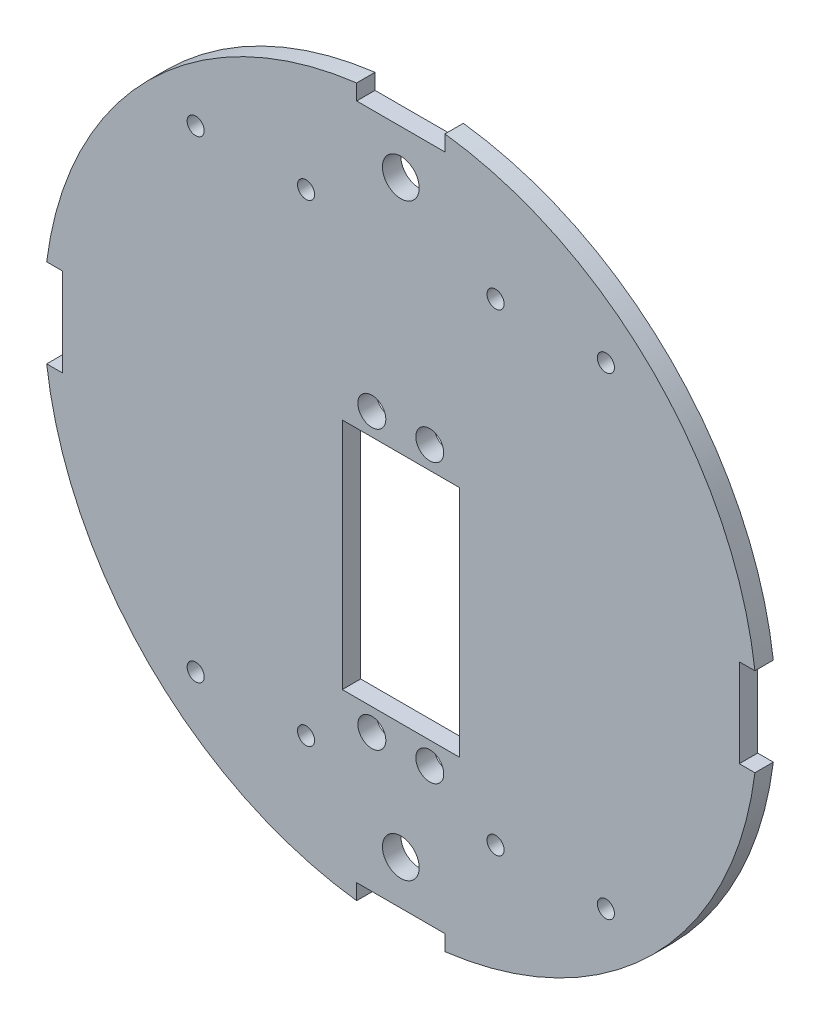
SolidWorks part; units mm, degrees
material "A-Glass Fiber"
ref_plane "Front Plane" through (0, 0, 0) normal (0, 0, 1) x (1, 0, 0)
ref_plane "Top Plane" through (0, 0, 0) normal (0, 1, 0) x (1, 0, 0)
ref_plane "Right Plane" through (0, 0, 0) normal (1, 0, 0) x (0, 0, -1)
sketch "Sketch1" plane through (0, 0, 0) normal (0, 0, 1) x (1, 0, 0)
  circle A0 centre (0, 0) radius 61.595
extrude "Boss-Extrude1" add sketch "Sketch1" along normal blind 3.175
sketch "Sketch2" plane through (0, 0, 3.175) normal (0, 0, 1) x (1, 0, 0)
  line L0 (0, 0) -> (0, 61.595) construction
  line L2 (-7.62, 58.42) -> (7.62, 58.42)
  line L3 (-7.62, 58.42) -> (-7.62, 64.77)
  line L4 (-7.62, 64.77) -> (7.62, 64.77)
  line L5 (7.62, 58.42) -> (7.62, 64.77)
  line L6 (-7.62, 58.42) -> (7.62, 64.77) construction
  line L7 (-7.62, 64.77) -> (7.62, 58.42) construction
  circle A0 centre (0, 0) radius 61.595 construction
  circle A1 centre (0, 50.8) radius 3.175
  dimension "D3" = 50.8
  dimension "D1" = 15.24
  dimension "D2" = 6.35
extrude "Cut-Extrude1" cut sketch "Sketch2" against normal blind 3.175 contours L5 L4 L3 L2 | A1
pattern_circular "CirPattern1" count 4 every 90 about axis through (0, 0, 3.175) along (0, 0, 1) of "Cut-Extrude1"
sketch "Sketch3" plane through (0, 0, 3.175) normal (0, 0, 1) x (1, 0, 0)
  line L2 (-10.1, 9.5) -> (-10.1, -29.8)
  line L3 (10.1, 9.5) -> (-10.1, 9.5)
  line L6 (10.1, -29.8) -> (10.1, 8.5)
  line L7 (-9.1, -30.8) -> (9.1, -30.8)
  line L8 (-9.1, -30.8) -> (-10.1, -30.8)
  line L9 (-10.1, -30.8) -> (-10.1, -29.8)
  line L10 (9.1, -30.8) -> (10.1, -30.8)
  line L11 (10.1, -30.8) -> (10.1, -29.8)
  line L12 (10.1, 8.5) -> (10.1, 9.5)
extrude "Cut-Extrude2" cut sketch "Sketch3" against normal blind 3.175
sketch "Sketch4" plane through (0, 0, 0) normal (0, 0, -1) x (-1, 0, 0)
  circle A0 centre (5, -34.65) radius 2.413
  circle A1 centre (-5, -34.65) radius 2.413
  circle A2 centre (-5, 13.35) radius 2.413
  circle A3 centre (5, 13.35) radius 2.413
extrude "Cut-Extrude3" cut sketch "Sketch4" against normal blind 3.175
sketch "Sketch5" plane through (0, 0, 0) normal (0, 0, -1) x (-1, 0, 0)
  circle A0 centre (-50.8, 0) radius 3.175
  circle A1 centre (50.8, 0) radius 3.175
extrude "Boss-Extrude2" add sketch "Sketch5" against normal blind 3.175
sketch "Sketch6" plane through (0, 0, 3.175) normal (0, 0, 1) x (1, 0, 0)
  line L0 (0, 58.42) -> (0, -58.42) construction
  line L1 (-7.62, 58.42) -> (7.62, 58.42) construction
  line L2 (7.62, -58.42) -> (-7.62, -58.42) construction
  circle A0 centre (16.3543, 40.8119) radius 1.4732 construction
  circle A1 centre (35.4043, 40.8119) radius 1.4732 construction
  circle A2 centre (35.4043, -40.8119) radius 1.4732 construction
  circle A3 centre (16.3543, -40.8119) radius 1.4732 construction
  circle A4 centre (16.3543, 40.8119) radius 1.4732
  circle A5 centre (35.4043, 40.8119) radius 1.4732
  circle A6 centre (35.4043, -40.8119) radius 1.4732
  circle A7 centre (16.3543, -40.8119) radius 1.4732
  circle A8 centre (-16.3543, -40.8119) radius 1.4732
  circle A9 centre (-35.4043, -40.8119) radius 1.4732
  circle A10 centre (-35.4043, 40.8119) radius 1.4732
  circle A11 centre (-16.3543, 40.8119) radius 1.4732
extrude "Cut-Extrude4" cut sketch "Sketch6" against normal through all
